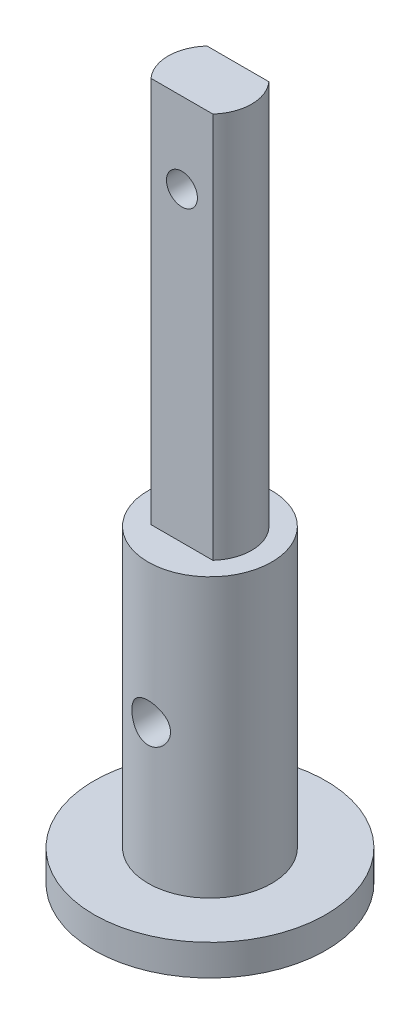
SolidWorks part; units mm, degrees
ref_plane "Front Plane" through (0, 0, 0) normal (0, 0, 1) x (1, 0, 0)
ref_plane "Top Plane" through (0, 0, 0) normal (0, 1, 0) x (1, 0, 0)
ref_plane "Right Plane" through (0, 0, 0) normal (1, 0, 0) x (0, 0, -1)
sketch "Sketch1" plane through (0, 0, 0) normal (0, 1, 0) x (1, 0, 0)
  circle A0 centre (0, 0) radius 7.5
  circle A1 centre (0, 0) radius 4
  dimension "D1" = 15
  dimension "D2" = 8
extrude "Boss-Extrude1" add sketch "Sketch1" along normal blind 2
extrude "Boss-Extrude2" add sketch "Sketch1<2>" along normal blind 45 contours A1 region at (0, 0, 0)
sketch "Sketch1<2>" plane through (0, 0, 0) normal (0, 1, 0) x (1, 0, 0) same geometry as "Sketch1"
sketch "Sketch2" plane through (0, 45, 0) normal (0, 1, 0) x (1, 0, 0)
  line L0 (-2, 1.8114) -> (2, 1.8114)
  line L1 (-3.8308, 0) -> (3.4281, 0) construction
  line L2 (-2, -1.8114) -> (2, -1.8114)
  arc A0 (-2, 1.8114) -> (-2, -1.8114) centre (0, 0) ccw
  arc A1 (2, -1.8114) -> (2, 1.8114) centre (0, 0) ccw
  circle A2 centre (0, 0) radius 4.5
extrude "Cut-Extrude1" cut sketch "Sketch2" against normal blind 25
sketch "Sketch3" plane through (0, 0, -1.8114) normal (0, 0, -1) x (-1, 0, 0)
  line L0 (0, 58.9249) -> (0, -1.0204) construction
  line L1 (4, 2) -> (-4, 2) construction
  circle A0 centre (0, 39.7943) radius 1
  circle A1 centre (0, 11) radius 1.25
  point P9 (0, 39.7943)
  dimension "D1" = 9
extrude "Cut-Extrude2" cut sketch "Sketch3" against normal blind 25 and the other way blind 25 contours A1 L0 | L0 A1 | L0 A0 | A0 L0 region at (-0.4244, 39.7943, -1.8114) region at (-0.5305, 11, -1.8114) region at (0.5305, 11, -1.8114) region at (0.4244, 39.7943, -1.8114)
